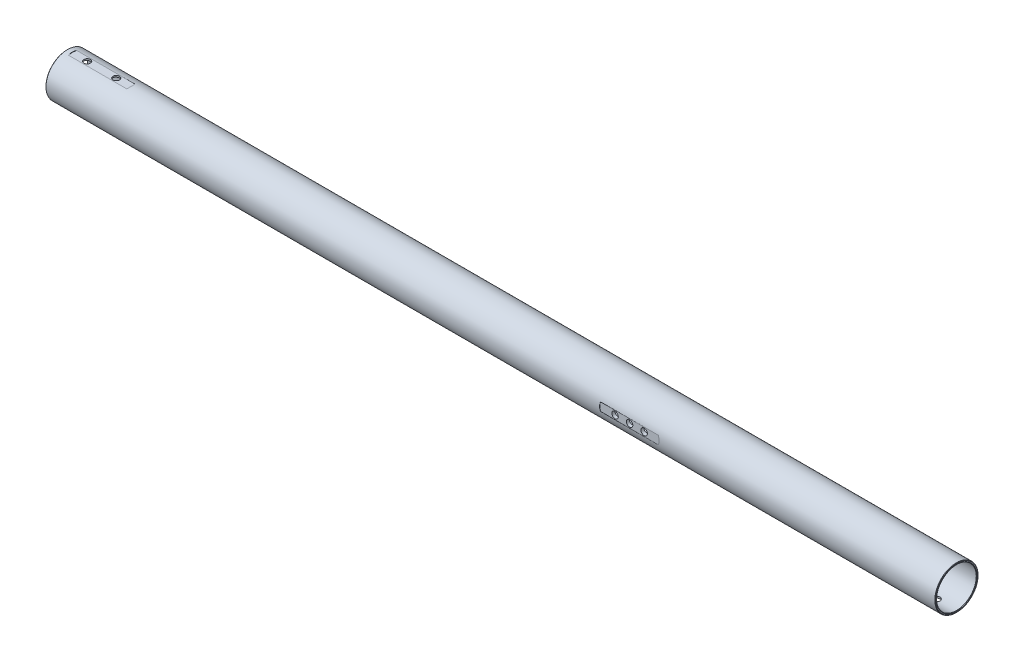
SolidWorks part; units mm, degrees
material "Stainless Steel (ferritic)"
ref_plane "Front Plane" through (0, 0, 0) normal (0, 0, 1) x (1, 0, 0)
ref_plane "Top Plane" through (0, 0, 0) normal (0, 1, 0) x (1, 0, 0)
ref_plane "Right Plane" through (0, 0, 0) normal (1, 0, 0) x (0, 0, -1)
sketch "Sketch1" plane through (0, 0, 0) normal (1, 0, 0) x (0, 0, -1)
  circle A0 centre (0, 0) radius 25
  dimension "D1" = 50
extrude "Extrude-Thin1" add sketch "Sketch1" along normal mid plane 1030 thin thin type one direction reverse wall 2
extrude "Extrude-Thin2" add sketch "Sketch1<3>" against normal blind 90 from offset 210 thin thin type one direction reverse wall 4
sketch "Sketch1<3>" plane through (0, 0, 0) normal (1, 0, 0) x (0, 0, -1) same geometry as "Sketch1"
sketch "Sketch3" plane through (0, 0, 0) normal (0, 1, 0) x (1, 0, 0)
  line L0 (-491.7775, 0) -> (-458.1225, 0) construction
  line L1 (-491.7775, 17.4725) -> (-458.1225, 17.4725)
  line L2 (-491.7775, -17.4725) -> (-458.1225, -17.4725)
  line L4 (-515, 25) -> (-515, -25) construction
  line L5 (0, -27.5) -> (0, 27.5) construction
  line L6 (491.7775, 0) -> (458.1225, 0) construction
  line L7 (491.7775, 17.4725) -> (458.1225, 17.4725)
  line L8 (491.7775, -17.4725) -> (458.1225, -17.4725)
  arc A1 (-491.7775, 17.4725) -> (-491.7775, -17.4725) centre (-491.7775, 0) ccw
  arc A2 (-458.1225, -17.4725) -> (-458.1225, 17.4725) centre (-458.1225, 0) ccw
  arc A3 (491.7775, 17.4725) -> (491.7775, -17.4725) centre (491.7775, 0) cw
  arc A4 (458.1225, -17.4725) -> (458.1225, 17.4725) centre (458.1225, 0) cw
  point P3 (-474.95, 0)
  point P14 (474.95, 0)
  dimension "D2" = 5.75
  dimension "D1" = 68.6
  dimension "D3" = 33.655
extrude "Cut-Extrude1" cut sketch "Sketch3" along normal through all from offset 24.54 contours L2 A2 L1 A1 region at (-474.95, 0, 0)
sketch "Sketch8" plane through (0, 0, 0) normal (0, 0, 1) x (1, 0, 0)
  line L0 (-272.5275, 0) -> (-238.8725, 0) construction
  line L1 (-272.5275, 17.4725) -> (-238.8725, 17.4725)
  line L2 (-272.5275, -17.4725) -> (-238.8725, -17.4725)
  line L4 (-515, 25) -> (-515, -25) construction
  line L5 (143.8725, 0) -> (177.5275, 0) construction
  line L6 (143.8725, 17.4725) -> (177.5275, 17.4725)
  line L7 (143.8725, -17.4725) -> (177.5275, -17.4725)
  line L13 (515, -25) -> (515, 25) construction
  arc A1 (-272.5275, 17.4725) -> (-272.5275, -17.4725) centre (-272.5275, 0) ccw
  arc A2 (-238.8725, -17.4725) -> (-238.8725, 17.4725) centre (-238.8725, 0) ccw
  arc A3 (143.8725, 17.4725) -> (143.8725, -17.4725) centre (143.8725, 0) ccw
  arc A4 (177.5275, -17.4725) -> (177.5275, 17.4725) centre (177.5275, 0) ccw
  point P3 (-255.7, 0)
  point P13 (160.7, 0)
  dimension "D2" = 225
  dimension "D1" = 68.6
  dimension "D3" = 33.655
  dimension "D6" = 320
  dimension "D4" = 68.6
  dimension "D5" = 33.655
extrude "Cut-Extrude2" cut sketch "Sketch8" against normal through all from offset 24.54 contours L2 A2 L1 A1 region at (-255.7, 0, 0) offset against normal yes
extrude "Cut-Extrude3" cut sketch "Sketch3<3>" against normal through all from offset 24.54 contours A4 L8 A3 L7 region at (474.95, 0, 0) offset against normal yes
sketch "Sketch3<3>" plane through (0, 0, 0) normal (0, 1, 0) x (1, 0, 0) same geometry as "Sketch3"
extrude "Cut-Extrude4" cut sketch "Sketch8<4>" along normal through all from offset 24.54 contours L7 A4 L6 A3 region at (160.7, 0, 0)
sketch "Sketch8<4>" plane through (0, 0, 0) normal (0, 0, 1) x (1, 0, 0) same geometry as "Sketch8"
sketch "Sketch11" plane through (0, 24.54, 0) normal (0, 1, 0) x (1, 0, 0)
  point P0 (-491.7775, 0)
  point P3 (-458.1225, 0)
hole_wizard "M (0.295) Diameter Hole3" positions "Sketch11" profile "Sketch12" hole size "M" standard "ANSI Inch" end condition up to next
sketch "Sketch12" plane through (-491.7775, 24.54, 0) normal (1, 0, 0) x (0, 0, 1)
  line L0 (0, 0) -> (0, 1.54)
  line L1 (0, 1.54) -> (3.7465, 1.54)
  line L2 (3.7465, 1.54) -> (3.7465, 0)
  line L5 (3.7465, 0) -> (0, 0)
  line L11 (0, -6.35) -> (0, 107.95) construction
  dimension "Thru Hole Dia." = 7.493
  dimension "Thru Hole Depth" = 1.54
sketch "Sketch13" plane through (0, 0, -24.54) normal (0, 0, -1) x (-1, 0, 0)
  point P0 (238.8725, 0)
  point P3 (272.5275, 0)
hole_wizard "M (0.295) Diameter Hole4" positions "Sketch13" profile "Sketch14" hole size "M" standard "ANSI Inch" end condition up to next
sketch "Sketch14" plane through (-238.8725, 0, -24.54) normal (1, 0, 0) x (0, 1, 0)
  line L0 (0, 0) -> (0, 1.54)
  line L1 (0, 1.54) -> (3.7465, 1.54)
  line L2 (3.7465, 1.54) -> (3.7465, 0)
  line L5 (3.7465, 0) -> (0, 0)
  line L11 (0, -6.35) -> (0, 107.95) construction
  dimension "Thru Hole Dia." = 7.493
  dimension "Thru Hole Depth" = 1.54
hole_wizard "M (0.295) Diameter Hole5" positions "Sketch15" profile "Sketch16" hole size "M" standard "ANSI Inch" end condition up to next
sketch "Sketch15" plane through (0, 0, 24.54) normal (0, 0, 1) x (1, 0, 0)
  point P0 (143.8725, 0)
  point P3 (160.7, 0)
  point P6 (177.5275, 0)
sketch "Sketch16" plane through (143.8725, 0, 24.54) normal (1, 0, 0) x (0, -1, 0)
  line L0 (0, 0) -> (0, 3.54)
  line L1 (0, 3.54) -> (3.7465, 3.54)
  line L2 (3.7465, 3.54) -> (3.7465, 0)
  line L5 (3.7465, 0) -> (0, 0)
  line L11 (0, -6.35) -> (0, 107.95) construction
  dimension "Thru Hole Dia." = 7.493
  dimension "Thru Hole Depth" = 3.54
sketch "Sketch18" plane through (0, -24.54, 0) normal (0, -1, 0) x (-1, 0, 0)
  point P0 (-491.7775, 0)
  point P3 (-458.1225, 0)
hole_wizard "M (0.295) Diameter Hole6" positions "Sketch18" profile "Sketch19" hole size "M" standard "ANSI Inch" end condition up to next
sketch "Sketch19" plane through (491.7775, -24.54, 0) normal (1, 0, 0) x (0, 0, -1)
  line L0 (0, 0) -> (0, 1.54)
  line L1 (0, 1.54) -> (3.7465, 1.54)
  line L2 (3.7465, 1.54) -> (3.7465, 0)
  line L5 (3.7465, 0) -> (0, 0)
  line L11 (0, -6.35) -> (0, 107.95) construction
  dimension "Thru Hole Dia." = 7.493
  dimension "Thru Hole Depth" = 1.54
chamfer "Chamfer1" distance 0.5 angle 45 4 edges at (-515, 0, -23) (-515, 0, -25) (515, 0, -23) (515, 0, -25)
